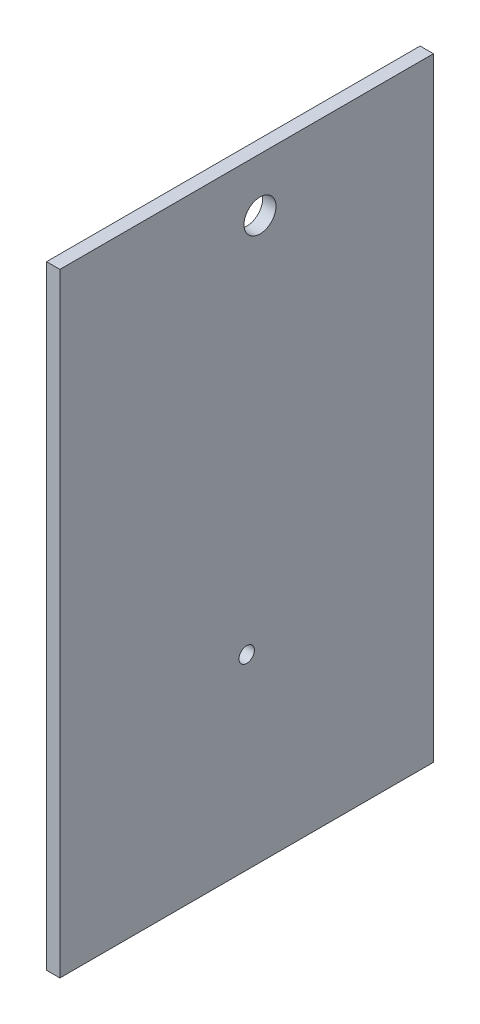
SolidWorks part; units mm, degrees
ref_plane "Front Plane" through (0, 0, 0) normal (0, 0, 1) x (1, 0, 0)
ref_plane "Top Plane" through (0, 0, 0) normal (0, 1, 0) x (1, 0, 0)
ref_plane "Right Plane" through (0, 0, 0) normal (1, 0, 0) x (0, 0, -1)
sketch "Sketch1" plane through (0, 0, 0) normal (1, 0, 0) x (0, 0, -1)
  line L1 (-44.45, 73.025) -> (44.45, 73.025)
  line L2 (-44.45, 73.025) -> (-44.45, -73.025)
  line L3 (-44.45, -73.025) -> (44.45, -73.025)
  line L4 (44.45, 73.025) -> (44.45, -73.025)
  line L5 (-44.45, 73.025) -> (44.45, -73.025) construction
  line L6 (-44.45, -73.025) -> (44.45, 73.025) construction
  point P0 (0, 0)
  dimension "D1" = 146.05
  dimension "D2" = 88.9
extrude "Boss-Extrude1" add sketch "Sketch1" along normal blind 3.175
sketch "Sketch2" plane through (3.175, 0, 0) normal (1, 0, 0) x (0, 0, -1)
  line L0 (-44.45, -73.025) -> (44.45, -73.025) construction
  line L1 (-44.45, 73.025) -> (-44.45, -73.025) construction
  circle A0 centre (3.175, 60.325) radius 3.81
  dimension "D3" = 7.62
  dimension "D1" = 133.35
  dimension "D2" = 47.625
extrude "Cut-Extrude1" cut sketch "Sketch2" against normal through all
sketch "Sketch3" plane through (0, 0, 0) normal (-1, 0, 0) x (0, 0, 1)
  line L0 (44.45, -73.025) -> (-44.45, -73.025) construction
  line L1 (-44.45, -73.025) -> (-44.45, 73.025) construction
  circle A0 centre (0, -28.575) radius 1.8288
  dimension "D3" = 3.6576
  dimension "D1" = 44.45
  dimension "D2" = 44.45
extrude "Cut-Extrude2" cut sketch "Sketch3" against normal through all
